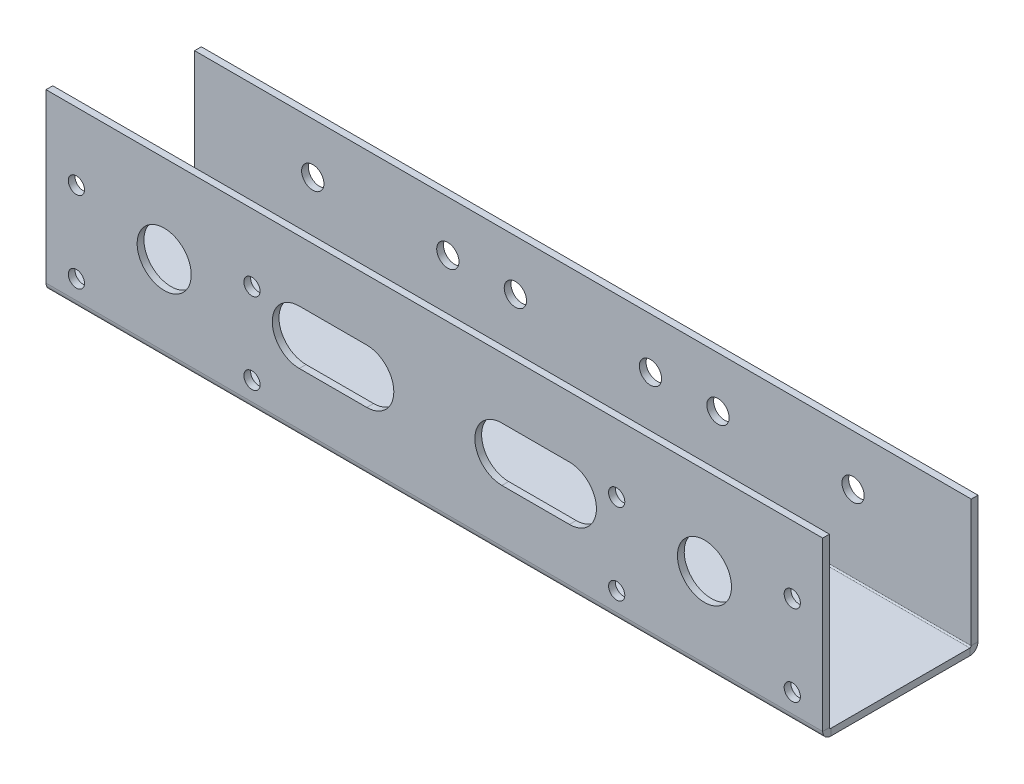
SolidWorks part; units mm, degrees
note: The reader was unsure of these and kept them because the rebuilt part matched: thickness of "Basis-Blech1", "Blech1", "Blech2", "Blech3"; bend radius of "Basisbiegung1", "Basisbiegung2".
material "Unlegierter Baustahl"
ref_plane "Ebene vorne" through (0, 0, 0) normal (0, 0, 1) x (1, 0, 0)
ref_plane "Ebene oben" through (0, 0, 0) normal (0, 1, 0) x (1, 0, 0)
ref_plane "Ebene rechts" through (0, 0, 0) normal (1, 0, 0) x (0, 0, -1)
sketch "Skizze1" plane through (0, 0, 0) normal (1, 0, 0) x (0, 0, -1)
  line L0 (-10.5, 25) -> (-10.5, 0)
  line L1 (-10.5, 0) -> (10.5, 0)
  line L2 (10.5, 0) -> (10.5, 19)
  dimension "D1" = 25
  dimension "D2" = 21
  dimension "D3" = 19
base flange "Basis-Blech1" sketch "Skizze1" end condition mid plane depth 115 reverse direction no thickness 1 reverse thickness direction no bend radius 0.2
bend "Basisbiegung1" bend radius 0.2 bend angle 90 parameters "D5"=1
bend "Basisbiegung2" bend radius 0.2 bend angle 90 parameters "D5"=2
sketch "Skizze6" plane through (0, 0, 11.5) normal (0, 0, 1) x (1, 0, 0)
  line L0 (-20, 12) -> (-10, 12) construction
  line L1 (-20, 16) -> (-10, 16)
  line L2 (-20, 8) -> (-10, 8)
  line L3 (0, 25) -> (0, 0) construction
  line L4 (57.5, 25) -> (-57.5, 25) construction
  line L5 (-40, 15) -> (-40, 3) construction
  line L6 (-53, 15) -> (-27, 15) construction
  line L7 (-53, 15) -> (-53, 3) construction
  line L8 (-53, 3) -> (-27, 3) construction
  line L9 (-27, 15) -> (-27, 3) construction
  line L10 (57.5, -1) -> (-57.5, -1) construction
  line L11 (20, 12) -> (10, 12) construction
  line L12 (20, 16) -> (10, 16)
  line L13 (20, 8) -> (10, 8)
  circle A0 centre (-40, 12) radius 4
  arc A1 (-20, 16) -> (-20, 8) centre (-20, 12) ccw
  arc A2 (-10, 8) -> (-10, 16) centre (-10, 12) ccw
  circle A3 centre (-53, 15) radius 1.2
  circle A4 centre (-53, 3) radius 1.2
  circle A5 centre (-27, 15) radius 1.2
  circle A6 centre (-27, 3) radius 1.2
  circle A7 centre (53, 3) radius 1.2
  arc A8 (20, 16) -> (20, 8) centre (20, 12) cw
  arc A9 (10, 8) -> (10, 16) centre (10, 12) cw
  circle A10 centre (27, 3) radius 1.2
  circle A11 centre (27, 15) radius 1.2
  circle A12 centre (40, 12) radius 4
  circle A13 centre (53, 15) radius 1.2
  point P4 (-15, 12)
  point P30 (15, 12)
  dimension "D1" = 8
  dimension "D6" = 2.4
  dimension "D2" = 10
  dimension "D3" = 10
  dimension "D4" = 20
  dimension "D5" = 12
  dimension "D7" = 26
  dimension "D8" = 4
  dimension "D9" = 9
extrude "Schnitt-Linear austragen1" cut sketch "Skizze6" against normal up to next normal cut yes
sketch "Skizze7" plane through (0, 0, -11.5) normal (0, 0, -1) x (-1, 0, 0)
  line L0 (-40, 11.5) -> (-20, 11.5) construction
  line L1 (-20, 11.5) -> (-10, 11.5) construction
  line L2 (-10, 11.5) -> (10, 11.5) construction
  line L3 (10, 11.5) -> (20, 11.5) construction
  line L4 (20, 11.5) -> (40, 11.5) construction
  line L5 (-57.5, 19) -> (57.5, 19) construction
  line L6 (0, 11.5) -> (0, 0) construction
  circle A0 centre (-40, 11.5) radius 1.65
  circle A1 centre (-20, 11.5) radius 1.65
  circle A2 centre (-10, 11.5) radius 1.65
  circle A3 centre (10, 11.5) radius 1.65
  circle A4 centre (20, 11.5) radius 1.65
  circle A5 centre (40, 11.5) radius 1.65
  dimension "D4" = 3.3
  dimension "D1" = 10
  dimension "D2" = 20
  dimension "D3" = 7.5
extrude "Schnitt-Linear austragen2" cut sketch "Skizze7" against normal up to next normal cut yes
sketch "Biegung-Linien1" plane through (0, 0, 0) normal (0, 1, 0) x (1, 0, 0)
sketch "Rahmen1" plane through (0, 0, 0) normal (0, 1, 0) x (1, 0, 0)
sheet metal parameters "Blech1" thickness 1 parameters "D1"=0.2
flat pattern "Abwicklung1" [suppressed]
sketch "Biegung-Linien2" plane through (0, 0, 0) normal (0, 1, 0) x (1, 0, 0)
sketch "Rahmen2" [suppressed] plane through (0, 0, 0) normal (0, 1, 0) x (1, 0, 0)
bend of the flat pattern "Abwickeln-<Basisbiegung1>1"
bend of the flat pattern "Abwickeln-<Basisbiegung2>1"
sheet metal parameters "Blech2" thickness 1 parameters "D1"=0.2
flat pattern "Abwicklung1" [suppressed]
sketch "Biegung-Linien2" plane through (0, 0, 0) normal (0, 1, 0) x (1, 0, 0)
sketch "Rahmen2" [suppressed] plane through (0, 0, 0) normal (0, 1, 0) x (1, 0, 0)
bend of the flat pattern "Abwickeln-<Basisbiegung1>1"
bend of the flat pattern "Abwickeln-<Basisbiegung2>1"
sheet metal parameters "Blech3" thickness 1 parameters "D1"=0.2
flat pattern "Abwicklung1" [suppressed]
sketch "Biegung-Linien2" plane through (0, 0, 0) normal (0, 1, 0) x (1, 0, 0)
sketch "Rahmen2" [suppressed] plane through (0, 0, 0) normal (0, 1, 0) x (1, 0, 0)
bend of the flat pattern "Abwickeln-<Basisbiegung1>1"
bend of the flat pattern "Abwickeln-<Basisbiegung2>1"
